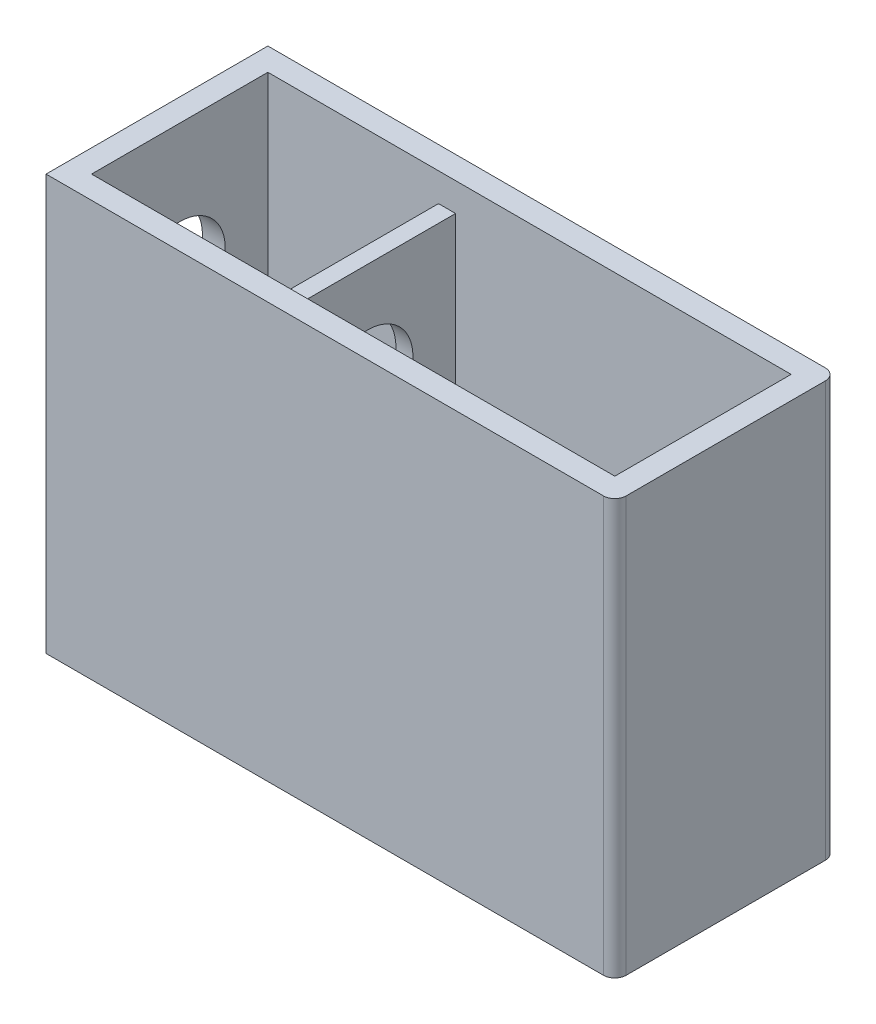
SolidWorks part; units mm, degrees
ref_plane "Front Plane" through (0, 0, 0) normal (0, 0, 1) x (1, 0, 0)
ref_plane "Top Plane" through (0, 0, 0) normal (0, 1, 0) x (1, 0, 0)
ref_plane "Right Plane" through (0, 0, 0) normal (1, 0, 0) x (0, 0, -1)
sketch "Sketch1" plane through (0, 0, 0) normal (0, 1, 0) x (1, 0, 0)
  line L0 (-46, 15.5) -> (-46, -15.5)
  line L1 (-50, 19.5) -> (50, 19.5)
  line L2 (-50, 19.5) -> (-50, -19.5)
  line L3 (-50, -19.5) -> (50, -19.5)
  line L4 (50, 19.5) -> (50, -19.5)
  line L5 (-50, 19.5) -> (50, -19.5) construction
  line L6 (-50, -19.5) -> (50, 19.5) construction
  line L7 (-46, -15.5) -> (46, -15.5)
  line L8 (46, 15.5) -> (46, -15.5)
  line L9 (-46, 15.5) -> (46, 15.5)
  point P0 (0, 0)
  dimension "D1" = 39
  dimension "D2" = 100
  dimension "D3" = 4
extrude "Boss-Extrude2" add sketch "Sketch1" along normal blind 3 contours L9 L0 L7 L8 region at (0, 0, 0)
extrude "Boss-Extrude3" add sketch "Sketch1<3>" along normal blind 73
sketch "Sketch1<3>" plane through (0, 0, 0) normal (0, 1, 0) x (1, 0, 0) same geometry as "Sketch1"
fillet "Fillet1" radius 2 1 edges at (50, 36.5, 19.5)
fillet "Fillet2" radius 2 1 edges at (50, 36.5, -19.5)
sketch "Sketch3" plane through (0, 3, 0) normal (0, 1, 0) x (1, 0, 0)
  line L0 (-46, 15.5) -> (46, 15.5) construction
  line L1 (46, -15.5) -> (38.86, -15.5)
  line L2 (46, -15.5) -> (46, 15.5)
  line L3 (46, 15.5) -> (38.86, 15.5)
  line L4 (38.86, -15.5) -> (38.86, 15.5)
  dimension "D1" = 7.14
extrude "Boss-Extrude4" add sketch "Sketch3" along normal blind 28
sketch "Sketch4" plane through (0, 31, 0) normal (0, 1, 0) x (1, 0, 0)
  line L0 (38.86, -7.08) -> (38.86, -9.931)
  line L1 (38.86, -7.08) -> (46, -7.08)
  line L2 (46, -15.5) -> (46, 15.5) construction
  line L3 (38.86, 15.5) -> (38.86, -15.5) construction
  line L4 (38.86, -9.931) -> (46, -9.931)
  line L5 (46, -9.931) -> (46, -7.08)
  circle A0 centre (43.36, 8.92) radius 0.5
  circle A1 centre (43.36, -1.08) radius 0.5
  line M9 (46, -15.5) -> (46, 15.5)
  line M11 (38.86, 15.5) -> (38.86, -15.5)
extrude "Boss-Extrude5" add sketch "Sketch4" along normal blind 4 contours L4 L1 M11 M9 region at (42.43, 31, 8.5055)
sketch "Sketch5" plane through (0, 31, 0) normal (0, 1, 0) x (1, 0, 0)
  line L4 (46, -15.5) -> (46, -9.931)
  line L5 (46, -9.931) -> (38.86, -9.931)
  line L6 (38.86, -9.931) -> (38.86, -15.5)
  line L7 (38.86, -15.5) -> (46, -15.5)
  line L8 (46, -15.5) -> (46, -9.931)
  line L9 (46, -9.931) -> (38.86, -9.931)
  line L10 (38.86, -9.931) -> (38.86, -15.5)
  line L11 (38.86, -15.5) -> (46, -15.5)
  dimension "D1" = 0
extrude "Cut-Extrude1" cut sketch "Sketch5" against normal blind 28
extrude "Cut-Extrude3" cut sketch "Sketch4<3>" against normal blind 20 contours A1 | A0
sketch "Sketch4<3>" plane through (0, 31, 0) normal (0, 1, 0) x (1, 0, 0) same geometry as "Sketch4"
pattern_linear "LPattern5" count 2 spacing 47.64 along (-1, 0, 0) of "Boss-Extrude4", "Boss-Extrude5", "Cut-Extrude1"
pattern_linear "LPattern6" count 2 spacing 49 along (-1, 0, 0) of "Cut-Extrude3"
sketch "Sketch10" plane through (38.86, 0, 0) normal (-1, 0, 0) x (0, 0, 1)
  line L1 (7.08, 35) -> (9.931, 35)
  line L2 (7.08, 35) -> (7.08, 3)
  line L3 (7.08, 3) -> (9.931, 3)
  line L4 (9.931, 35) -> (9.931, 3)
extrude "Boss-Extrude6" add sketch "Sketch10" along normal blind 41
sketch "Sketch12" plane through (-46, 0, 0) normal (1, 0, 0) x (0, 0, -1)
  line L1 (15.5, 73) -> (15.5, 3) construction
  line L2 (15.5, 50) -> (-15.5, 50)
  line L3 (-15.5, 73) -> (-15.5, 3) construction
  circle A0 centre (0, 50) radius 8
extrude "Cut-Extrude4" cut sketch "Sketch12" along normal blind 36 and the other way blind 35 contours L2 A0 | L2 A0 region at (-46, 46.6047, 0) region at (-46, 53.3953, 0)
sketch "Sketch13" plane through (0, 3, 0) normal (0, 1, 0) x (1, 0, 0)
  line L0 (46, 15.5) -> (-46, 15.5) construction
  line L1 (-16, 15.5) -> (-13, 15.5)
  line L2 (-16, 15.5) -> (-16, -15.5)
  line L3 (-16, -15.5) -> (-13, -15.5)
  line L4 (-13, 15.5) -> (-13, -15.5)
  line L5 (-46, -15.5) -> (46, -15.5) construction
  dimension "D1" = 3
extrude "Boss-Extrude7" add sketch "Sketch13" along normal blind 65
sketch "Sketch14" plane through (-16, 0, 0) normal (-1, 0, 0) x (0, 0, 1)
  circle A0 centre (0, 50) radius 8
extrude "Cut-Extrude5" cut sketch "Sketch14" against normal blind 5
